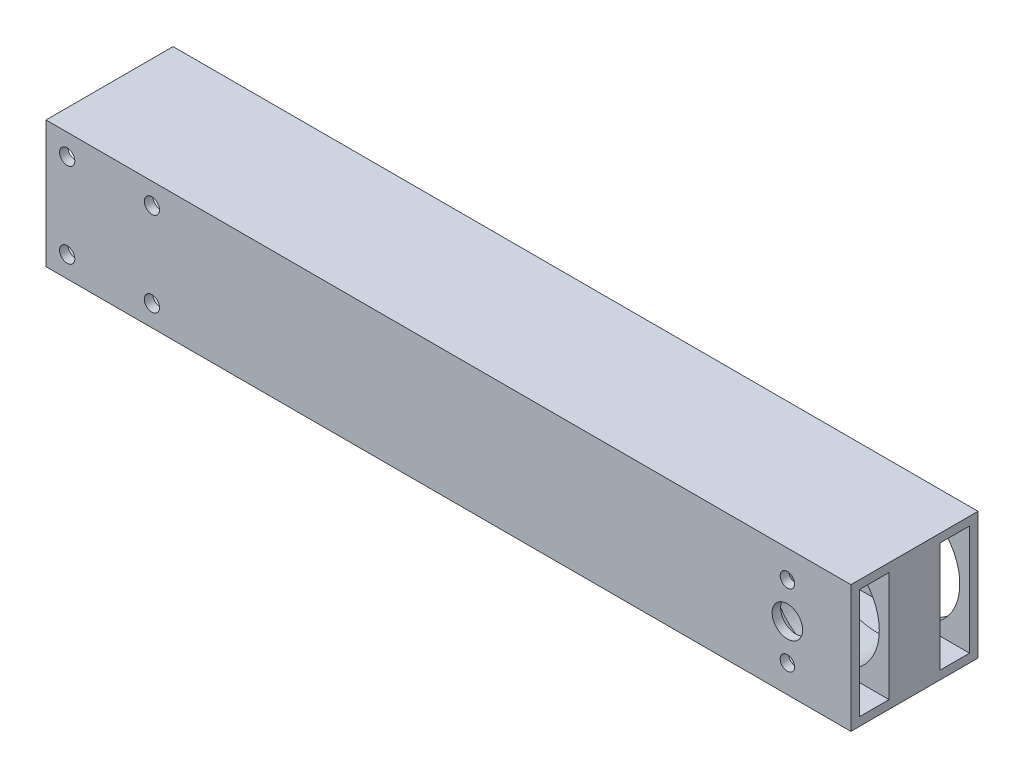
SolidWorks part; units mm, degrees
material "PLA 15%"
ref_plane "Front Plane" through (0, 0, 0) normal (0, 0, 1) x (1, 0, 0)
ref_plane "Top Plane" through (0, 0, 0) normal (0, 1, 0) x (1, 0, 0)
ref_plane "Right Plane" through (0, 0, 0) normal (1, 0, 0) x (0, 0, -1)
sketch "Sketch1" plane through (0, 0, 0) normal (1, 0, 0) x (0, 0, -1)
  line L1 (-15, -15) -> (15, -15)
  line L2 (-15, -15) -> (-15, 15)
  line L3 (-15, 15) -> (15, 15)
  line L4 (15, -15) -> (15, 15)
  line L5 (-15, -15) -> (15, 15) construction
  line L6 (-15, 15) -> (15, -15) construction
  line L11 (-5.1844, 5.1844) -> (5.1844, -5.1844) construction
  line L12 (-5.1844, -5.1844) -> (5.1844, 5.1844) construction
  line L13 (-13, 13) -> (-6, 13)
  line L14 (-13, 13) -> (-13, -13)
  line L15 (-13, -13) -> (-6, -13)
  line L16 (-6, 13) -> (-6, -13)
  line L17 (13, 13) -> (6, 13)
  line L18 (13, 13) -> (13, -13)
  line L19 (13, -13) -> (6, -13)
  line L20 (6, 13) -> (6, -13)
  point P0 (0, 0)
  point P7 (0, 0)
  dimension "D1" = 30
  dimension "D2" = 30
  dimension "D3" = 2
  dimension "D4" = 7
  dimension "D5" = 2
  dimension "D6" = 7
  dimension "D7" = 2
  dimension "D8" = 2
extrude "Boss-Extrude3" add sketch "Sketch1" along normal blind 110 and the other way blind 80
sketch "Sketch6" plane through (0, 0, -15) normal (0, 0, -1) x (-1, 0, 0)
  line L0 (-110, -15) -> (-110, 15) construction
  line L2 (-110, 0) -> (80, 0) construction
  line L3 (80, -15) -> (80, 15) construction
  circle A0 centre (-95, 0) radius 12.7
  dimension "D2" = 25.4
  dimension "D1" = 15
extrude "Cut-Extrude5" cut sketch "Sketch6" against normal blind 23
sketch "Sketch8" plane through (0, 0, 15) normal (0, 0, 1) x (1, 0, 0)
  line L0 (110, 15) -> (110, -15) construction
  circle A0 centre (95, 0) radius 3.6
  circle A1 centre (95, 8.5) radius 1.7
  circle A2 centre (95, -8.5) radius 1.7
  dimension "D2" = 7.2
  dimension "D5" = 3.4
  dimension "D1" = 15
  dimension "D3" = 8.5
  dimension "D4" = 8.5
extrude "Cut-Extrude6" cut sketch "Sketch8" against normal blind 17
sketch "Sketch9" plane through (-80, 0, 0) normal (-1, 0, 0) x (0, 0, 1)
  line L0 (-6, 13) -> (6, 13)
  line L1 (-6, -13) -> (6, -13)
  line L2 (-6, 13) -> (-6, -13)
  line L3 (6, 13) -> (6, -13)
extrude "Cut-Extrude7" cut sketch "Sketch9" against normal blind 155
sketch "Sketch13" plane through (0, 0, 15) normal (0, 0, 1) x (1, 0, 0)
  line L4 (-55, 10) -> (-55, -10) construction
  line L8 (-75, -10) -> (105, -10)
  line L9 (105, -10) -> (105, 10)
  line L10 (105, 10) -> (-75, 10)
  line L11 (-75, 10) -> (-75, -10)
  line L12 (-75, -10) -> (-55, -10) construction
  line L14 (-55, 10) -> (-75, 10) construction
  line L15 (-75, 10) -> (-75, -10) construction
  point P6 (-75, -10)
  point P8 (-55, -10)
  point P10 (-55, 10)
  point P11 (-75, 10)
  dimension "D1" = 5
hole_wizard "M3 Clearance Hole1" positions "Sketch13" profile "Sketch14" hole size "M3" standard "ANSI Metric" end condition through all
sketch "Sketch14" plane through (-75, 10, 15) normal (1, 0, 0) x (0, -1, 0)
  line L0 (0, 0) -> (0, 30)
  line L1 (0, 30) -> (1.8, 30)
  line L2 (1.8, 30) -> (1.8, 0)
  line L5 (1.8, 0) -> (0, 0)
  line L11 (0, -6.35) -> (0, 107.95) construction
  dimension "Thru Hole Dia." = 3.6
  dimension "Thru Hole Depth" = 30
